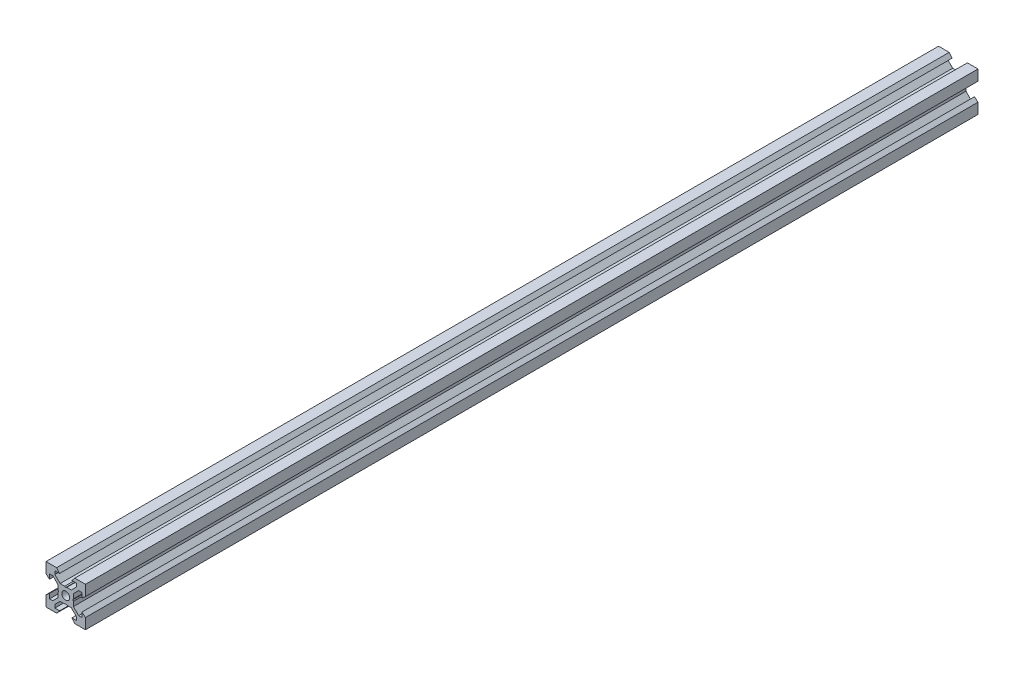
SolidWorks part; units mm, degrees
ref_plane "Front Plane" through (0, 0, 0) normal (0, 0, 1) x (1, 0, 0)
ref_plane "Top Plane" through (0, 0, 0) normal (0, 1, 0) x (1, 0, 0)
ref_plane "Right Plane" through (0, 0, 0) normal (1, 0, 0) x (0, 0, -1)
sketch "Sketch1" plane through (0, 0, 0) normal (0, 0, 1) x (1, 0, 0)
  line L0 (10, 10) -> (4.6104, 10) construction
  line L1 (10, 10) -> (10, 4.6104) construction
  line L2 (10, -10) -> (10, -4.6104) construction
  line L3 (10, -10) -> (4.6104, -10) construction
  line L4 (10, 10) -> (10, 4.6104)
  line L5 (6.5607, 5.5) -> (8.2, 5.5)
  line L6 (5.5, 8.2) -> (5.5, 6.5607)
  line L7 (10, 10) -> (4.6104, 10)
  line L8 (10, 10) -> (10, 4.6104)
  line L9 (6.5607, 5.5) -> (3.9, 2.8393)
  line L10 (5.5, 6.5607) -> (2.8393, 3.9)
  line L11 (10, 4.6104) -> (8.2, 3.1)
  line L12 (4.6104, 10) -> (3.1, 8.2)
  line L13 (8.2, 3.1) -> (8.2, 5.5)
  line L14 (3.1, 8.2) -> (5.5, 8.2)
  line L15 (-6.5607, 5.5) -> (-8.2, 5.5)
  line L16 (6.5607, -5.5) -> (8.2, -5.5)
  line L17 (3.1, -8.2) -> (5.5, -8.2)
  line L18 (8.2, -3.1) -> (8.2, -5.5)
  line L19 (4.6104, -10) -> (3.1, -8.2)
  line L20 (10, -4.6104) -> (8.2, -3.1)
  line L21 (0.5196, -3.9) -> (0, -3.6)
  line L22 (0.5196, 3.9) -> (0, 3.6)
  line L23 (3.6, 0) -> (3.9, -0.5196)
  line L24 (3.9, 0.5196) -> (3.6, 0)
  line L25 (3.9, 0.5196) -> (3.9, 2.8393)
  line L26 (2.8393, 3.9) -> (0.5196, 3.9)
  line L27 (3.9, -2.8393) -> (3.9, -0.5196)
  line L28 (2.8393, -3.9) -> (0.5196, -3.9)
  line L29 (5.5, -6.5607) -> (2.8393, -3.9)
  line L30 (6.5607, -5.5) -> (3.9, -2.8393)
  line L31 (10, -10) -> (10, -4.6104)
  line L32 (10, -10) -> (4.6104, -10)
  line L33 (5.5, -8.2) -> (5.5, -6.5607)
  line L34 (-6.5607, -5.5) -> (-8.2, -5.5)
  line L35 (10, -10) -> (10, -4.6104)
  line L36 (0, 0) -> (0, 8.2) construction
  line L37 (-10, -10) -> (-4.6104, -10) construction
  line L38 (-10, -10) -> (-10, -4.6104) construction
  line L39 (-10, 10) -> (-10, 4.6104) construction
  line L40 (-10, 10) -> (-4.6104, 10) construction
  line L41 (-10, -10) -> (-10, -4.6104)
  line L43 (-5.5, -8.2) -> (-5.5, -6.5607)
  line L44 (-10, -10) -> (-4.6104, -10)
  line L45 (-10, -10) -> (-10, -4.6104)
  line L46 (-6.5607, -5.5) -> (-3.9, -2.8393)
  line L47 (-5.5, -6.5607) -> (-2.8393, -3.9)
  line L48 (-2.8393, -3.9) -> (-0.5196, -3.9)
  line L49 (-3.9, -2.8393) -> (-3.9, -0.5196)
  line L50 (-2.8393, 3.9) -> (-0.5196, 3.9)
  line L51 (-3.9, 0.5196) -> (-3.9, 2.8393)
  line L52 (-3.9, 0.5196) -> (-3.6, 0)
  line L53 (-3.6, 0) -> (-3.9, -0.5196)
  line L54 (-0.5196, 3.9) -> (0, 3.6)
  line L55 (-0.5196, -3.9) -> (0, -3.6)
  line L56 (-10, -4.6104) -> (-8.2, -3.1)
  line L57 (-4.6104, -10) -> (-3.1, -8.2)
  line L58 (-8.2, -3.1) -> (-8.2, -5.5)
  line L59 (-3.1, -8.2) -> (-5.5, -8.2)
  line L60 (-10, -10) -> (10, -10) construction
  line L61 (-10, -10) -> (-10, 10) construction
  line L62 (-3.1, 8.2) -> (-5.5, 8.2)
  line L63 (-8.2, 3.1) -> (-8.2, 5.5)
  line L64 (-4.6104, 10) -> (-3.1, 8.2)
  line L65 (-10, 4.6104) -> (-8.2, 3.1)
  line L66 (-5.5, 6.5607) -> (-2.8393, 3.9)
  line L67 (-6.5607, 5.5) -> (-3.9, 2.8393)
  line L68 (-10, 10) -> (-10, 4.6104)
  line L69 (-10, 10) -> (-4.6104, 10)
  line L70 (-5.5, 8.2) -> (-5.5, 6.5607)
  line L71 (-10, 10) -> (10, 10) construction
  line L72 (-10, 10) -> (-10, 4.6104)
  line L73 (10, -10) -> (10, 10) construction
  line L74 (-10, -10) -> (10, 10) construction
  line L75 (-10, 10) -> (10, -10) construction
  circle A0 centre (0, 0) radius 2
  dimension "D7" = 4
  dimension "D1" = 20
  dimension "D2" = 5.3896
  dimension "D3" = 4.5
  dimension "D4" = 50
  dimension "D5" = 1.8
  dimension "D6" = 1.5104
  dimension "D8" = 5.5
  dimension "D9" = 120
  dimension "D10" = 0.3
  dimension "D11" = 2.3197
  dimension "D12" = 7.8
  dimension "D13" = 7.8
  dimension "D14" = 1.5
  dimension "D15" = 2.6607
extrude "Boss-Extrude1" add sketch "Sketch1" along normal mid plane 452.69 contours L70 L62 L64 L69 L68 L65 L63 L15 L67 L51 L52 L53 L49 L46 L34 L58 L56 L41 L44 L57 L59 L43 L47 L48 L55 L21 L28 L29 L33 L17 L19 L32 L31 L20 L18 L16 L30 L27 L23 L24 L25 L9 L5 L13 L11 L4 L7 L12 L14 L6 L10 region at (9.7172, 7.3052, 0)
